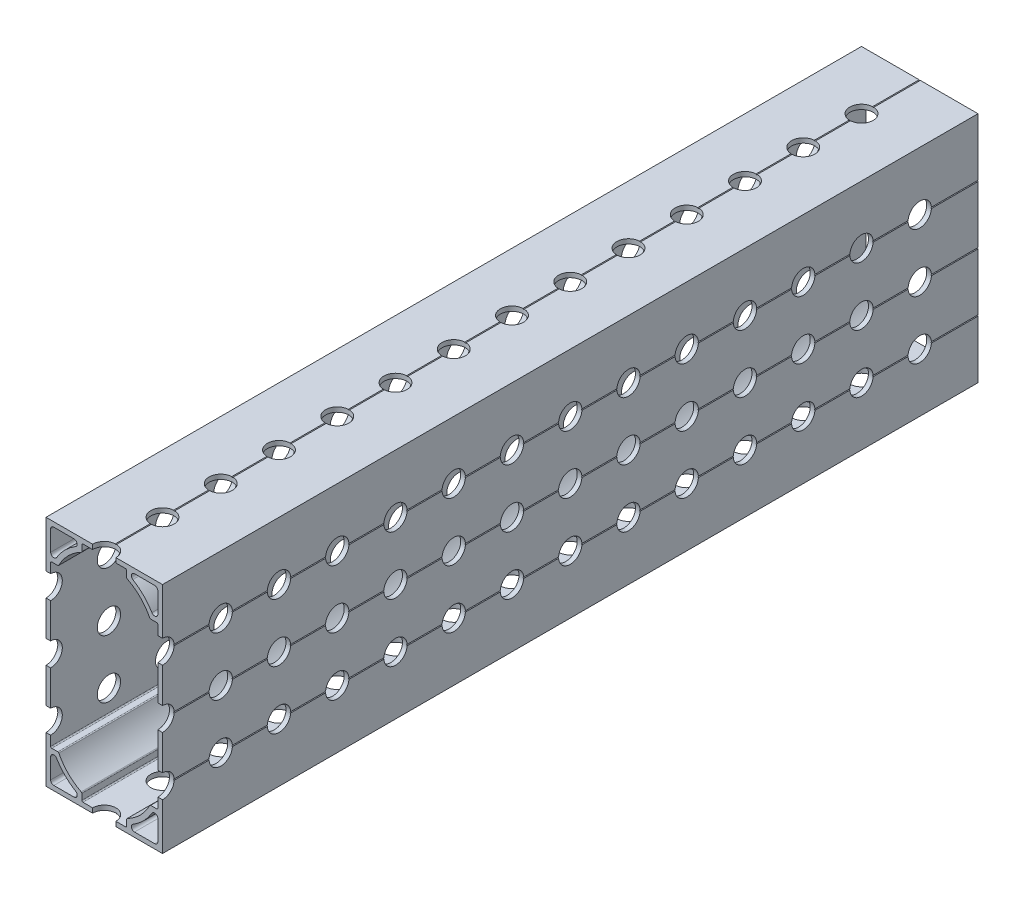
SolidWorks part; units mm, degrees
ref_plane "Front Plane" through (0, 0, 0) normal (0, 0, 1) x (1, 0, 0)
ref_plane "Top Plane" through (0, 0, 0) normal (0, 1, 0) x (1, 0, 0)
ref_plane "Right Plane" through (0, 0, 0) normal (1, 0, 0) x (0, 0, -1)
other "Configuration Table"
sketch "Sketch3" plane through (0, 0, 0) normal (0, 0, 1) x (1, 0, 0)
  line L0 (0, 12.7) -> (0, -12.7) construction
  line L1 (12.7, -25.4) -> (0.127, -25.4)
  line L2 (12.7, -12.827) -> (12.7, -25.4)
  line L3 (12.573, -12.7) -> (12.7, -12.827)
  line L4 (-10.9924, -24.384) -> (-6.5971, -24.384)
  line L5 (-11.684, -19.2971) -> (-11.684, -23.6924)
  line L6 (12.7, -12.573) -> (12.573, -12.7)
  line L7 (12.7, -0.127) -> (12.7, -12.573)
  line L10 (12.573, 0) -> (12.7, -0.127)
  line L11 (0.127, -25.4) -> (0, -25.273)
  line L14 (11.684, 0) -> (11.684, -17.5895)
  line L15 (11.684, -17.5895) -> (9.979, -17.5895)
  line L18 (4.8895, -22.679) -> (4.8895, -24.384)
  line L19 (11.684, -19.2971) -> (11.684, -23.6924)
  line L20 (10.9924, -24.384) -> (6.5971, -24.384)
  line L21 (55, 0) -> (-55, 0) construction
  line L37 (12.573, 0) -> (12.7, 0.127)
  line L46 (-4.8895, -24.384) -> (4.8895, -24.384)
  line L47 (-4.8895, -22.679) -> (-4.8895, -24.384)
  line L48 (-11.684, -17.5895) -> (-9.979, -17.5895)
  line L49 (-11.684, 0) -> (-11.684, -17.5895)
  line L57 (-0.127, 25.4) -> (-12.7, 25.4)
  line L58 (-12.7, 12.827) -> (-12.7, 25.4)
  line L59 (-12.573, 12.7) -> (-12.7, 12.827)
  line L60 (-12.7, 12.573) -> (-12.573, 12.7)
  line L61 (-12.7, 0.127) -> (-12.7, 12.573)
  line L62 (-12.573, 0) -> (-12.7, 0.127)
  line L63 (-0.127, 25.4) -> (0, 25.273)
  line L64 (-11.684, 0) -> (-11.684, 17.5895)
  line L65 (-11.684, 17.5895) -> (-9.979, 17.5895)
  line L66 (-4.8895, 22.679) -> (-4.8895, 24.384)
  line L67 (-4.8895, 24.384) -> (4.8895, 24.384)
  line L69 (10.9924, 24.384) -> (6.5971, 24.384)
  line L70 (11.684, 19.2971) -> (11.684, 23.6924)
  line L71 (4.8895, 22.679) -> (4.8895, 24.384)
  line L72 (11.684, 17.5895) -> (9.979, 17.5895)
  line L73 (11.684, 0) -> (11.684, 17.5895)
  line L74 (0.127, 25.4) -> (0, 25.273)
  line L76 (12.7, 0.127) -> (12.7, 12.573)
  line L77 (12.7, 12.573) -> (12.573, 12.7)
  line L78 (-11.684, 19.2971) -> (-11.684, 23.6924)
  line L79 (-10.9924, 24.384) -> (-6.5971, 24.384)
  line L80 (12.573, 12.7) -> (12.7, 12.827)
  line L81 (12.7, 12.827) -> (12.7, 25.4)
  line L82 (12.7, 25.4) -> (0.127, 25.4)
  line L96 (-0.127, -25.4) -> (0, -25.273)
  line L118 (-12.573, 0) -> (-12.7, -0.127)
  line L119 (-12.7, -0.127) -> (-12.7, -12.573)
  line L120 (-12.7, -12.573) -> (-12.573, -12.7)
  line L121 (-12.573, -12.7) -> (-12.7, -12.827)
  line L122 (-12.7, -12.827) -> (-12.7, -25.4)
  line L123 (-12.7, -25.4) -> (-0.127, -25.4)
  arc A0 (9.979, -17.5895) -> (4.8895, -22.679) centre (0, -12.7) cw
  arc A1 (6.5971, -24.384) -> (6.2412, -23.0994) centre (6.5971, -23.6924) cw
  arc A2 (10.3994, -18.9412) -> (6.2412, -23.0994) centre (0, -12.7) cw
  arc A3 (10.3994, -18.9412) -> (11.684, -19.2971) centre (10.9924, -19.2971) cw
  arc A4 (11.684, -23.6924) -> (10.9924, -24.384) centre (10.9924, -23.6924) cw
  arc A10 (-11.684, -23.6924) -> (-10.9924, -24.384) centre (-10.9924, -23.6924) ccw
  arc A11 (-10.3994, -18.9412) -> (-11.684, -19.2971) centre (-10.9924, -19.2971) ccw
  arc A12 (-10.3994, -18.9412) -> (-6.2412, -23.0994) centre (0, -12.7) ccw
  arc A14 (-6.5971, -24.384) -> (-6.2412, -23.0994) centre (-6.5971, -23.6924) ccw
  arc A24 (-9.979, 17.5895) -> (-4.8895, 22.679) centre (0, 12.7) cw
  arc A25 (-6.5971, 24.384) -> (-6.2412, 23.0994) centre (-6.5971, 23.6924) cw
  arc A30 (-10.3994, 18.9412) -> (-6.2412, 23.0994) centre (0, 12.7) cw
  arc A31 (-10.3994, 18.9412) -> (-11.684, 19.2971) centre (-10.9924, 19.2971) cw
  arc A32 (-11.684, 23.6924) -> (-10.9924, 24.384) centre (-10.9924, 23.6924) cw
  arc A33 (11.684, 23.6924) -> (10.9924, 24.384) centre (10.9924, 23.6924) ccw
  arc A34 (10.3994, 18.9412) -> (11.684, 19.2971) centre (10.9924, 19.2971) ccw
  arc A35 (10.3994, 18.9412) -> (6.2412, 23.0994) centre (0, 12.7) ccw
  arc A41 (6.5971, 24.384) -> (6.2412, 23.0994) centre (6.5971, 23.6924) ccw
  arc A42 (9.979, 17.5895) -> (4.8895, 22.679) centre (0, 12.7) ccw
  arc A46 (-9.979, -17.5895) -> (-4.8895, -22.679) centre (0, -12.7) ccw
  point P71 (0, -24.384)
  point P104 (-11.684, -8.7948)
  point P108 (11.684, -8.7948)
  point P130 (11.684, 8.7948)
  point P131 (-11.684, 8.7948)
  point P132 (0, 24.384)
  dimension "D4" = 0.6916
  dimension "D7" = 11.1125
  dimension "D14" = 12.1285
  dimension "D1" = 25.4
  dimension "D2" = 12.573
  dimension "D3" = 5.7785
  dimension "D5" = 12.7
  dimension "D6" = 4.8895
  dimension "D8" = 1.016
  dimension "D9" = 135
  dimension "D10" = 0.127
  dimension "D11" = 1.016
  dimension "D12" = 135
  dimension "D13" = 135
extrude "Boss-Extrude1" add sketch "Sketch3" along normal blind 177.8 contours L48 A46 L47 L46 L18 A0 L15 L14 L73 L72 A42 L71 L67 L66 A24 L65 L64 L49 | A32 L78 A31 A30 A25 L79 | L69 A41 A35 A34 L70 A33 | L4 A14 A12 A11 L5 A10 | A4 L19 A3 A2 A1 L20 | L57 L58 L59 L60 L61 L62 L118 L119 L120 L121 L122 L123 L96 L11 L1 L2 L3 L6 L7 L10 L37 L76 L77 L80 L81 L82 L74 L63 region at (-9.5535, -22.2535, 0) region at (0, 0, 0) region at (9.5535, -22.2535, 0) region at (9.5535, 22.2535, 0) region at (-9.5535, 22.2535, 0)
sketch "Sketch2" plane through (25.4, 25.4, 0) normal (0, -1, 0) x (0, 0, 1)
  line L2 (177.8, 25.4) -> (0, 25.4) construction
  line L3 (0, 12.7) -> (0, 25.273) construction
  circle A0 centre (12.7, 25.4) radius 2.54
  dimension "D1" = 5.08
  dimension "D2" = 12.7
extrude "Cut-Extrude1" cut sketch "Sketch2" along normal through all
pattern_linear "LPattern1" count 95 spacing 12.7 along (0, 0, 1) of "Cut-Extrude1"
fillet "Fillet1" radius 0.254 16 edges at (9.979, 17.5895, 88.9) (11.684, 17.5895, 88.9) (4.8895, 22.679, 88.9) (4.8895, 24.384, 88.9) (11.684, -17.5895, 88.9) (9.979, -17.5895, 88.9) (4.8895, -22.679, 88.9) (4.8895, -24.384, 88.9) (-4.8895, -22.679, 88.9) (-4.8895, -24.384, 88.9) (-9.979, -17.5895, 88.9) (-11.684, -17.5895, 88.9) (-4.8895, 24.384, 88.9) (-4.8895, 22.679, 88.9) (-11.684, 17.5895, 88.9) (-9.979, 17.5895, 88.9)
sketch "Sketch4" plane through (12.7, 0, 0) normal (1, 0, 0) x (0, 0, -1)
  line L0 (-177.8, 12.7) -> (0, 12.7) construction
  line L1 (-177.8, 0) -> (0, 0) construction
  line L2 (-177.8, -12.7) -> (0, -12.7) construction
  line L3 (0, 12.827) -> (0, 25.4) construction
  circle A0 centre (-12.7, 12.7) radius 2.54
  circle A1 centre (-12.7, 0) radius 2.54
  circle A2 centre (-12.7, -12.7) radius 2.54
  dimension "D1" = 2.54
  dimension "D2" = 12.7
extrude "Cut-Extrude2" cut sketch "Sketch4" against normal through all
pattern_linear "LPattern2" count 94 spacing 12.7 along (0, 0, 1) of "Cut-Extrude2"
equation "\"Length\" = 7"
equation "\"D1@Boss-Extrude1\"=\"Length\""
